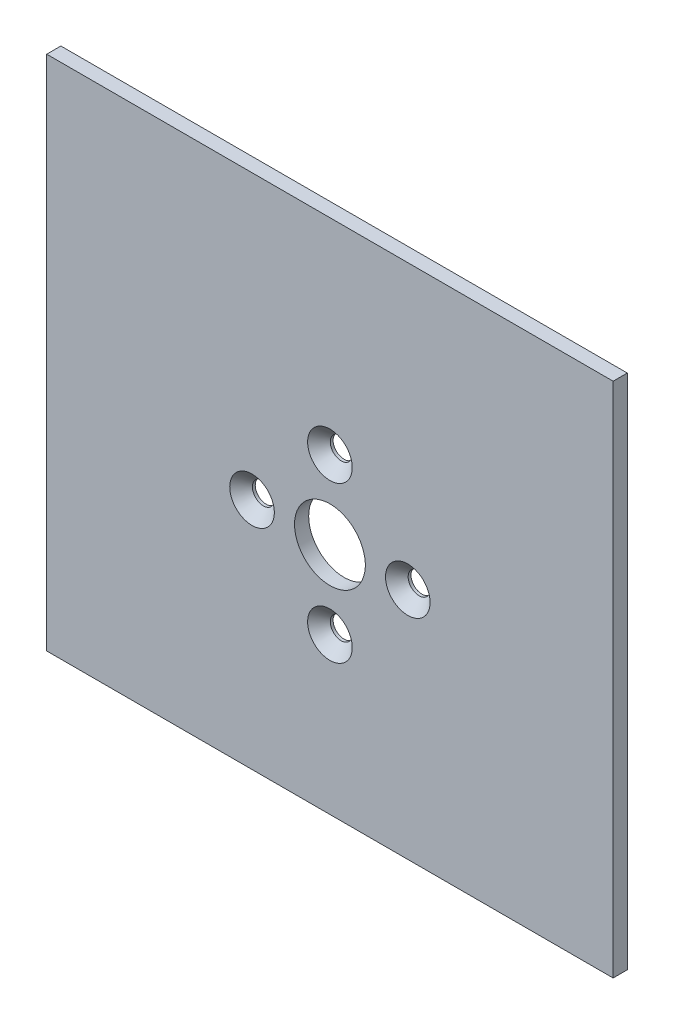
SolidWorks part; units mm, degrees
ref_plane "前视基准面" through (0, 0, 0) normal (0, 0, 1) x (1, 0, 0)
ref_plane "上视基准面" through (0, 0, 0) normal (0, 1, 0) x (1, 0, 0)
ref_plane "右视基准面" through (0, 0, 0) normal (1, 0, 0) x (0, 0, -1)
sketch "草图1" plane through (0, 0, -1.3) normal (0, 0, -1) x (-1, 0, 0)
  line L0 (52.9761, 0) -> (-56.7794, 0) construction
  line L1 (0, 22.1223) -> (0, -22.869) construction
  line L3 (40, 40) -> (-40, 40)
  line L4 (40, 40) -> (40, -33)
  line L5 (40, -33) -> (-40, -33)
  line L6 (-40, 40) -> (-40, -33)
  circle A0 centre (0, 0) radius 5 construction
  circle A1 centre (0, 0) radius 5
  dimension "D1" = 40
  dimension "D2" = 80
  dimension "D3" = 33
extrude "凸台-拉伸1" add sketch "草图1" along normal blind 2
hole_wizard "打孔尺寸(%根据十字)槽沉头自攻螺钉的类型1" positions "草图2" profile "草图3" countersink size "ST2.9" standard "GB"
sketch "草图2" plane through (0, 0, -1.3) normal (0, 0, 1) x (1, 0, 0)
  point P0 (11, 0)
  dimension "D1" = 11
sketch "草图3" plane through (11, 0, -1.3) normal (1, 0, 0) x (0, -1, 0)
  line L0 (0, 0) -> (0, 5.4313)
  line L1 (0, 5.4313) -> (1.55, 4.5)
  line L2 (1.55, 4.5) -> (1.55, 1.6)
  line L3 (1.55, 1.6) -> (3.15, 0)
  line L5 (3.15, 0) -> (0, 0)
  line L6 (-1.55, 1.6) -> (-3.15, 0) construction
  line L10 (0, 5.4313) -> (-1.55, 4.5) construction
  line L11 (0, -6.35) -> (0, 107.95) construction
  dimension "孔直径" = 3.1
  dimension "孔深度" = 4.5
  dimension "近端锥形沉头孔直径" = 6.3
  dimension "近端锥形沉头孔角度" = 90
  dimension "导头角度" = 118
pattern_circular "阵列(圆周)1" count 4 over 360 about axis through (0, 0, -3.3) along (0, 0, -1) of "打孔尺寸(%根据十字)槽沉头自攻螺钉的类型1"
